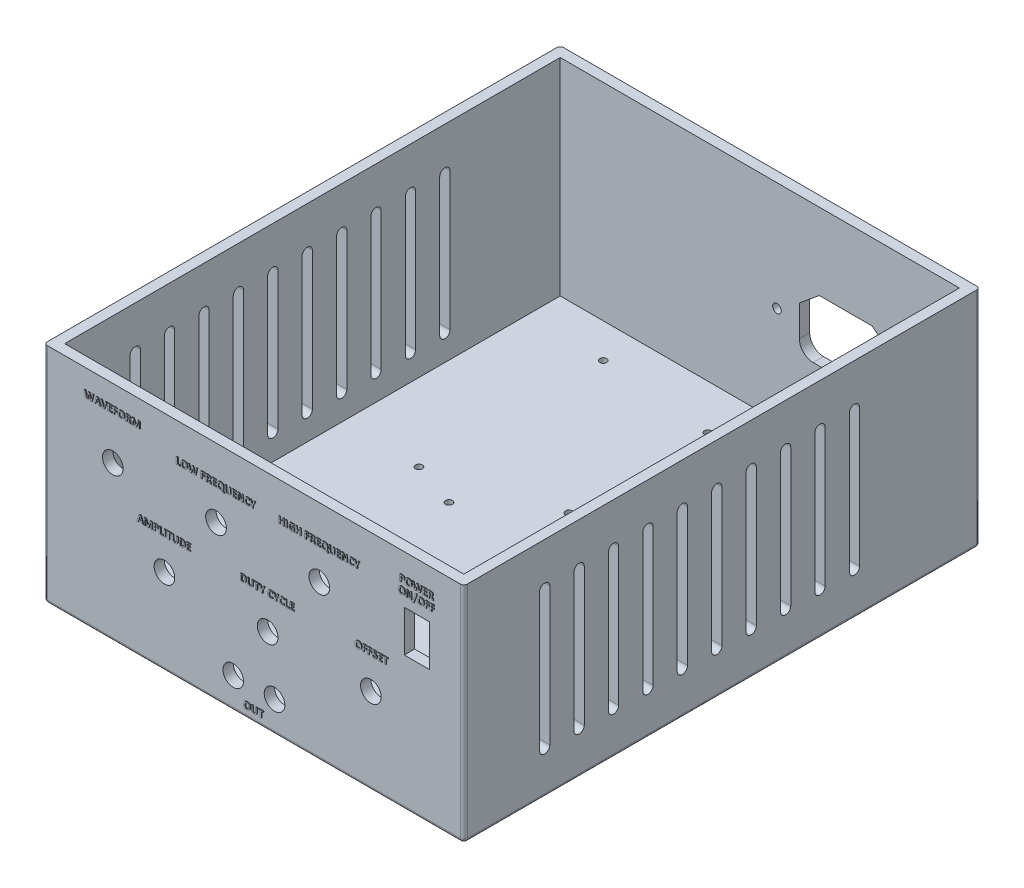
SolidWorks part; units mm, degrees
ref_plane "Front Plane" through (0, 0, 0) normal (0, 0, 1) x (1, 0, 0)
ref_plane "Top Plane" through (0, 0, 0) normal (0, 1, 0) x (1, 0, 0)
ref_plane "Right Plane" through (0, 0, 0) normal (1, 0, 0) x (0, 0, -1)
sketch "Sketch1" plane through (0, 0, 0) normal (0, 1, 0) x (1, 0, 0)
  line L1 (0, 0) -> (122, 0)
  line L2 (0, 0) -> (0, 150)
  line L3 (0, 150) -> (122, 150)
  line L4 (122, 0) -> (122, 150)
  dimension "D1" = 122
  dimension "D2" = 150
extrude "Boss-Extrude1" add sketch "Sketch1" along normal blind 65
sketch "Sketch2" plane through (0, 65, 0) normal (0, 1, 0) x (1, 0, 0)
  line L8 (3, 147) -> (3, 3)
  line L9 (3, 3) -> (119, 3)
  line L10 (119, 3) -> (119, 147)
  line L11 (119, 147) -> (3, 147)
  line L12 (3, 147) -> (3, 3)
  line L13 (3, 3) -> (119, 3)
  line L14 (119, 3) -> (119, 147)
  line L15 (119, 147) -> (3, 147)
  dimension "D1" = 3
extrude "Cut-Extrude1" cut sketch "Sketch2" against normal offset from surface (60 mm away) 5 up to face at (61, 0, -75)
sketch "Sketch3" plane through (0, 0, 0) normal (0, 0, 1) x (1, 0, 0)
  line L0 (0, 0) -> (122, 0) construction
  line L1 (0, 65) -> (0, 0) construction
  circle A0 centre (20, 45) radius 3
  circle A1 centre (50, 45) radius 3
  circle A2 centre (65, 25) radius 3
  circle A3 centre (95, 25) radius 3
  circle A4 centre (80, 45) radius 3
  circle A5 centre (35, 25) radius 3
  point P14 (0, 0)
  point P15 (0, 0)
  point P16 (36.9285, 26.102)
  point P17 (0, 0)
  point P18 (0, 0)
  point P19 (0, 0)
  point P20 (0, 0)
  point P21 (0, 0)
  dimension "D1" = 6
  dimension "D2" = 6
  dimension "D3" = 6
  dimension "D4" = 6
  dimension "D5" = 6
  dimension "D6" = 6
  dimension "D14" = 30
  dimension "D9" = 30
  dimension "D10" = 30
  dimension "D11" = 30
  dimension "D7" = 25
  dimension "D8" = 20
  dimension "D13" = 20
extrude "Cut-Extrude2" cut sketch "Sketch3" against normal blind 5
sketch "Sketch4" plane through (0, 0, 0) normal (0, 0, 1) x (1, 0, 0)
  line L1 (104.7, 51) -> (112, 51)
  line L2 (104.7, 51) -> (104.7, 39)
  line L3 (104.7, 39) -> (112, 39)
  line L4 (112, 51) -> (112, 39)
  line L5 (122, 65) -> (122, 0) construction
  point P4 (104.7, 45)
  dimension "D1" = 7.3
  dimension "D2" = 12
  dimension "D4" = 10
extrude "Cut-Extrude3" cut sketch "Sketch4" against normal blind 10
sketch "Sketch5" plane through (0, 0, 0) normal (0, 0, 1) x (1, 0, 0)
  line L2 (67, 9) -> (55, 9) construction
  line L3 (0, 0) -> (122, 0) construction
  circle A3 centre (55, 9) radius 3
  circle A4 centre (67, 9) radius 3
  point P0 (61, 9)
  point P3 (61, 0)
  dimension "D4" = 6
  dimension "D5" = 6
  dimension "D10" = 12
extrude "Cut-Extrude4" cut sketch "Sketch5" against normal blind 8
sketch "Sketch6" plane through (0, 0, 0) normal (-1, 0, 0) x (0, 0, 1)
  line L0 (-150, 65) -> (-150, 0) construction
  line L1 (-115, 52.5) -> (-112, 52.5) construction
  line L2 (-115, 52.5) -> (-115, 12.5)
  line L3 (-115, 12.5) -> (-112, 12.5) construction
  line L4 (-112, 52.5) -> (-112, 12.5)
  line L5 (-105, 52.5) -> (-105, 12.5)
  line L6 (-102, 52.5) -> (-102, 12.5)
  line L7 (-95, 52.5) -> (-95, 12.5)
  line L8 (-92, 52.5) -> (-92, 12.5)
  line L9 (-85, 52.5) -> (-85, 12.5)
  line L10 (-82, 52.5) -> (-82, 12.5)
  line L11 (-75, 52.5) -> (-75, 12.5)
  line L12 (-72, 52.5) -> (-72, 12.5)
  line L13 (-65, 52.5) -> (-65, 12.5)
  line L14 (-62, 52.5) -> (-62, 12.5)
  line L15 (-55, 52.5) -> (-55, 12.5)
  line L16 (-52, 52.5) -> (-52, 12.5)
  line L17 (-45, 52.5) -> (-45, 12.5)
  line L18 (-42, 52.5) -> (-42, 12.5)
  line L19 (-35, 52.5) -> (-35, 12.5)
  line L20 (-32, 52.5) -> (-32, 12.5)
  line L21 (-25, 52.5) -> (-25, 12.5)
  line L22 (-22, 52.5) -> (-22, 12.5)
  arc A0 (-112, 52.5) -> (-115, 52.5) centre (-113.5, 52.5) ccw
  arc A1 (-115, 12.5) -> (-112, 12.5) centre (-113.5, 12.5) ccw
  arc A2 (-102, 52.5) -> (-105, 52.5) centre (-103.5, 52.5) ccw
  arc A3 (-105, 12.5) -> (-102, 12.5) centre (-103.5, 12.5) ccw
  arc A4 (-92, 52.5) -> (-95, 52.5) centre (-93.5, 52.5) ccw
  arc A5 (-95, 12.5) -> (-92, 12.5) centre (-93.5, 12.5) ccw
  arc A6 (-82, 52.5) -> (-85, 52.5) centre (-83.5, 52.5) ccw
  arc A7 (-85, 12.5) -> (-82, 12.5) centre (-83.5, 12.5) ccw
  arc A8 (-72, 52.5) -> (-75, 52.5) centre (-73.5, 52.5) ccw
  arc A9 (-75, 12.5) -> (-72, 12.5) centre (-73.5, 12.5) ccw
  arc A10 (-62, 52.5) -> (-65, 52.5) centre (-63.5, 52.5) ccw
  arc A11 (-65, 12.5) -> (-62, 12.5) centre (-63.5, 12.5) ccw
  arc A12 (-52, 52.5) -> (-55, 52.5) centre (-53.5, 52.5) ccw
  arc A13 (-55, 12.5) -> (-52, 12.5) centre (-53.5, 12.5) ccw
  arc A14 (-42, 52.5) -> (-45, 52.5) centre (-43.5, 52.5) ccw
  arc A15 (-45, 12.5) -> (-42, 12.5) centre (-43.5, 12.5) ccw
  arc A16 (-32, 52.5) -> (-35, 52.5) centre (-33.5, 52.5) ccw
  arc A17 (-35, 12.5) -> (-32, 12.5) centre (-33.5, 12.5) ccw
  arc A18 (-22, 52.5) -> (-25, 52.5) centre (-23.5, 52.5) ccw
  arc A19 (-25, 12.5) -> (-22, 12.5) centre (-23.5, 12.5) ccw
  point P4 (-115, 32.5)
  point P7 (-150, 32.5)
  dimension "D3" = 35
  dimension "D1" = 40
  dimension "D2" = 3
  dimension "D4" = 10
extrude "Cut-Extrude5" cut sketch "Sketch6" against normal through all
sketch "Sketch7" plane through (0, 5, 0) normal (0, 1, 0) x (1, 0, 0)
  circle A0 centre (41.596, 55.004) radius 1
  circle A1 centre (38.802, 78.88) radius 1
  circle A2 centre (95.698, 79.134) radius 1
  circle A3 centre (95.444, 26.81) radius 1
  dimension "D1" = 2
  dimension "D2" = 2
  dimension "D3" = 2
  dimension "D4" = 2
extrude "Cut-Extrude6" cut sketch "Sketch7" against normal up to surface (5 mm away) up to face at (61, 0, -75)
sketch "Sketch8" plane through (0, 5, 0) normal (0, 1, 0) x (1, 0, 0)
  circle A0 centre (101, 134.045) radius 1
  circle A1 centre (101, 93.69) radius 1
  circle A2 centre (58.867, 134.045) radius 1
  circle A3 centre (58.867, 93.69) radius 1
  dimension "D1" = 2
  dimension "D2" = 2
  dimension "D3" = 2
  dimension "D4" = 2
extrude "Cut-Extrude7" cut sketch "Sketch8" against normal blind 5
sketch "Sketch9" plane through (0, 0, 0) normal (0, -1, 0) x (1, 0, 0)
  circle A0 centre (95.444, -26.81) radius 2.1
  circle A1 centre (95.698, -79.134) radius 2.1
  circle A2 centre (101, -93.69) radius 2.1
  circle A3 centre (58.867, -134.045) radius 2.1
  circle A4 centre (41.596, -55.004) radius 2.1
  circle A5 centre (38.802, -78.88) radius 2.1
  circle A6 centre (58.867, -93.69) radius 2.1
  circle A7 centre (101, -134.045) radius 2.1
  dimension "D1" = 4.2
  dimension "D2" = 4.2
  dimension "D3" = 4.2
  dimension "D4" = 4.2
  dimension "D5" = 4.2
  dimension "D6" = 4.2
  dimension "D7" = 4.2
  dimension "D8" = 4.2
extrude "Cut-Extrude8" cut sketch "Sketch9" against normal blind 2
sketch "Sketch10" plane through (0, 0, 0) normal (0, 0, 1) x (1, 0, 0)
  line L0 (5.0103, 57.5) -> (34.9917, 57.5) construction
  text T0 "WAVEFORM" font "Calibri" height 2
  point P2 (20.001, 57.5)
  point P4 (34.9917, 57.5)
  dimension "D1" = 12.5
  dimension "D2" = 0.001
extrude "Boss-Extrude2" add sketch "Sketch10" along normal blind 0.2 separate body
sketch "Sketch11" plane through (0, 0, 0) normal (0, 0, 1) x (1, 0, 0)
  line L0 (37.4718, 54) -> (62.5302, 54) construction
  text T0 "LOW FREQUENCY" font "Calibri" height 2
  point P2 (50.001, 54)
  point P5 (62.5302, 54)
  dimension "D1" = 9
  dimension "D2" = 0.001
extrude "Boss-Extrude3" add sketch "Sketch11" along normal blind 0.2 separate body
sketch "Sketch12" plane through (0, 0, 0) normal (0, 0, 1) x (1, 0, 0)
  line L0 (67.1248, 54) -> (92.8772, 54) construction
  text T0 "HIGH FREQUENCY" font "Calibri" height 2
  point P2 (80.001, 54)
  point P5 (92.8772, 54)
  dimension "D1" = 9
  dimension "D2" = 0.001
extrude "Boss-Extrude4" add sketch "Sketch12" along normal blind 0.2 separate body
sketch "Sketch13" plane through (0, 0, 0) normal (0, 0, 1) x (1, 0, 0)
  line L0 (25.7248, 34) -> (44.2772, 34) construction
  text T0 "AMPLITUDE" font "Calibri" height 2
  point P2 (35.001, 34)
  point P5 (36.75, 33.0447)
  point P6 (44.2772, 34)
  dimension "D1" = 9
  dimension "D2" = 0.001
extrude "Boss-Extrude5" add sketch "Sketch13" along normal blind 0.2 separate body
sketch "Sketch14" plane through (0, 0, 0) normal (0, 0, 1) x (1, 0, 0)
  line L0 (55.7665, 34) -> (74.2355, 34) construction
  text T0 "DUTY CYCLE" font "Calibri" height 2
  point P2 (65.001, 34)
  dimension "D1" = 0.001
  dimension "D2" = 9
extrude "Boss-Extrude6" add sketch "Sketch14" along normal blind 0.2 separate body
sketch "Sketch15" plane through (0, 0, 0) normal (0, 0, 1) x (1, 0, 0)
  line L0 (90.4205, 34) -> (99.5815, 34) construction
  text T0 "OFFSET" font "Calibri" height 2
  point P2 (95.001, 34)
  point P6 (95.9959, 35.4928)
  dimension "D1" = 0.001
  dimension "D2" = 9
extrude "Boss-Extrude7" add sketch "Sketch15" along normal blind 0.2 separate body
sketch "Sketch16" plane through (0, 0, 0) normal (0, 0, 1) x (1, 0, 0)
  line L0 (101.87, 57) -> (114.83, 57) construction
  line L1 (102.108, 54) -> (114.592, 54) construction
  line L2 (112, 51) -> (104.7, 51) construction
  text T0 "POWER" font "Calibri" height 2
  text T1 "ON/OFF" font "Calibri" height 2
  point P4 (108.35, 54)
  point P5 (108.35, 57)
  point P8 (108.35, 51)
  dimension "D1" = 3
  dimension "D2" = 3
extrude "Boss-Extrude8" add sketch "Sketch16" along normal blind 0.2 separate body
sketch "Sketch18" plane through (0, 0, 0) normal (0, 0, 1) x (1, 0, 0)
  line L0 (56, 2.5) -> (66, 2.5) construction
  text T0 "OUT" font "Calibri" height 2
  point P2 (0, 0)
  point P3 (0, 0)
  dimension "D1" = 6.5
  dimension "D2" = 1
  dimension "D3" = 1
extrude "Boss-Extrude10" add sketch "Sketch18" along normal blind 0.2 separate body
sketch "Sketch21" plane through (0, 5, 0) normal (0, 1, 0) x (1, 0, 0)
  circle A0 centre (25.5, 137) radius 1
  circle A1 centre (25.5, 83.4695) radius 1
  dimension "D1" = 2
  dimension "D2" = 2
extrude "Cut-Extrude10" cut sketch "Sketch21" against normal through all
sketch "Sketch22" plane through (0, 0, 0) normal (0, -1, 0) x (1, 0, 0)
  circle A0 centre (25.5, -83.4695) radius 1.5
  circle A1 centre (25.5, -137) radius 2.1
  dimension "D1" = 4.2
extrude "Cut-Extrude11" cut sketch "Sketch22" against normal blind 2
sketch "Sketch25" plane through (0, 0, -150) normal (0, 0, -1) x (-1, 0, 0)
  line L0 (-99.5, 38) -> (-93.7, 42.755)
  line L1 (-93.7, 42.755) -> (-78.3, 42.755)
  line L2 (-99.5, 38) -> (-99.5, 29)
  line L3 (-95.5, 25) -> (-76.5, 25)
  line L4 (-72.5, 38) -> (-72.5, 29)
  line L5 (-78.3, 42.755) -> (-72.5, 38)
  line L6 (-122, 65) -> (-122, 0) construction
  line L7 (-122, 0) -> (0, 0) construction
  arc A0 (-76.5, 25) -> (-72.5, 29) centre (-76.5, 29) ccw
  arc A1 (-95.5, 25) -> (-99.5, 29) centre (-95.5, 29) cw
  point P0 (-86, 42.755)
  point P3 (-86, 25)
  point P10 (-72.5, 25)
  point P13 (-99.5, 25)
  dimension "D6" = 4
  dimension "D1" = 15.4
  dimension "D2" = 7.5
  dimension "D3" = 9
  dimension "D4" = 27
  dimension "D5" = 7.5
  dimension "D7" = 22.5
  dimension "D8" = 25
extrude "Cut-Extrude12" cut sketch "Sketch25" against normal up to surface (3 mm away) up to face at (61, 35, -147)
sketch "Sketch27" plane through (0, 0, -150) normal (0, 0, -1) x (-1, 0, 0)
  circle A0 centre (-106, 33.355) radius 1.25
  circle A1 centre (-66, 33.355) radius 1.25
  dimension "D1" = 2.5
  dimension "D2" = 2.5
extrude "Cut-Extrude13" cut sketch "Sketch27" against normal up to surface (3 mm away) up to face at (86, 33.4816, -147)
sketch "Sketch28" plane through (0, 0, -150) normal (0, 0, -1) x (-1, 0, 0)
  line L0 (-97.584, 18.155) -> (-74.416, 18.155) construction
  line L1 (-72.5309, 22.155) -> (-99.4691, 22.155) construction
  line L2 (-95.5, 25) -> (-76.5, 25) construction
  text T0 "IN" font "Calibri" height 2
  point P6 (-86, 25)
  point P7 (-86, 18.155)
  dimension "D1" = 4
extrude "Boss-Extrude12" add sketch "Sketch28" along normal blind 0.2 separate body
fillet "Fillet1" radius 1 8 edges at (61, 0, 0) (122, 0, -75) (61, 0, -150) (0, 0, -75) (122, 32.5, 0) (122, 32.5, -150) (0, 32.5, -150) (0, 32.5, 0)
